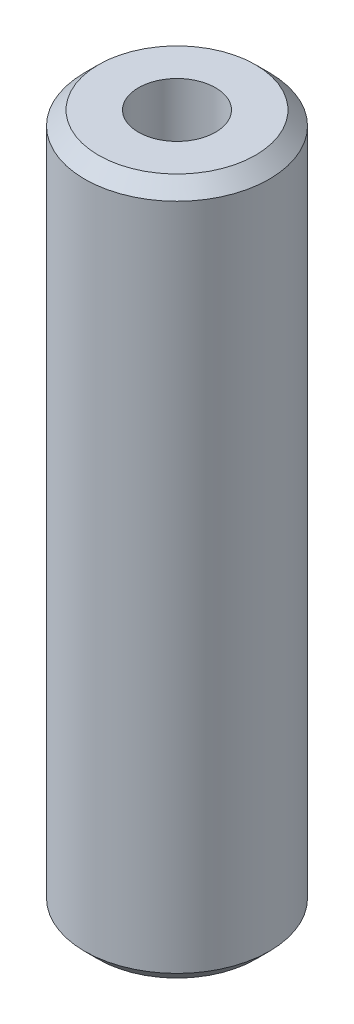
SolidWorks part; units mm, degrees
ref_plane "Front Plane" through (0, 0, 0) normal (0, 0, 1) x (1, 0, 0)
ref_plane "Top Plane" through (0, 0, 0) normal (0, 1, 0) x (1, 0, 0)
ref_plane "Right Plane" through (0, 0, 0) normal (1, 0, 0) x (0, 0, -1)
sketch "Sketch1" plane through (0, 0, 0) normal (0, 1, 0) x (1, 0, 0)
  circle A0 centre (0, 0) radius 30
  dimension "SHAFT_OD" = 60
extrude "Boss-Extrude1" add sketch "Sketch1" along normal blind 226.3323
sketch "Sketch2" plane through (0, 0, 0) normal (0, 1, 0) x (1, 0, 0)
  circle A0 centre (0, 0) radius 12.5357
  dimension "BORE_D" = 25.0715
extrude "Cut-Extrude1" cut sketch "Sketch2" along normal through all
chamfer "Chamfer1" distance 4.4909 angle 45 2 edges at (0, 226.3323, 30) (0, 0, 30)
